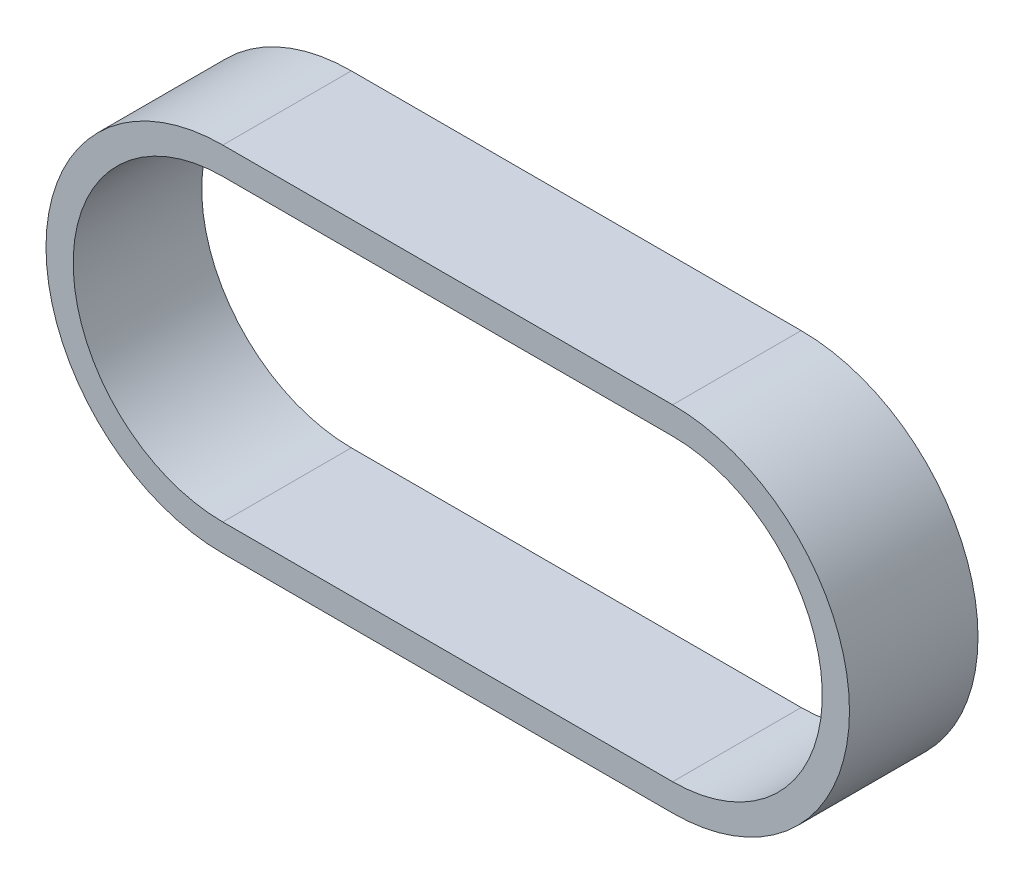
SolidWorks part; units mm, degrees
material "Rubber"
ref_plane "Front Plane" through (0, 0, 0) normal (0, 0, 1) x (1, 0, 0)
ref_plane "Top Plane" through (0, 0, 0) normal (0, 1, 0) x (1, 0, 0)
ref_plane "Right Plane" through (0, 0, 0) normal (1, 0, 0) x (0, 0, -1)
sketch "Sketch1" plane through (0, 0, 0) normal (0, 0, 1) x (1, 0, 0)
  line L0 (0, 20.6375) -> (52.5018, 20.6375)
  line L1 (0, 17.4625) -> (52.5018, 17.4625)
  line L2 (0, -17.4625) -> (52.5018, -17.4625)
  line L3 (0, -20.6375) -> (52.5018, -20.6375)
  arc A0 (0, 17.4625) -> (0, -17.4625) centre (0, 0) ccw
  arc A1 (0, 20.6375) -> (0, -20.6375) centre (0, 0) ccw
  arc A2 (52.5018, -20.6375) -> (52.5018, 20.6375) centre (52.5018, 0) ccw
  arc A3 (52.5018, -17.4625) -> (52.5018, 17.4625) centre (52.5018, 0) ccw
  point P1 (66.5167, -19.0971)
  point P8 (0, 0)
  point P12 (0, 0)
  point P14 (78.4008, 20.6375)
  dimension "D1" = 20.6375
  dimension "D2" = 17.4625
  dimension "D3" = 52.5018
extrude "Boss-Extrude1" add sketch "Sketch1" along normal blind 15
